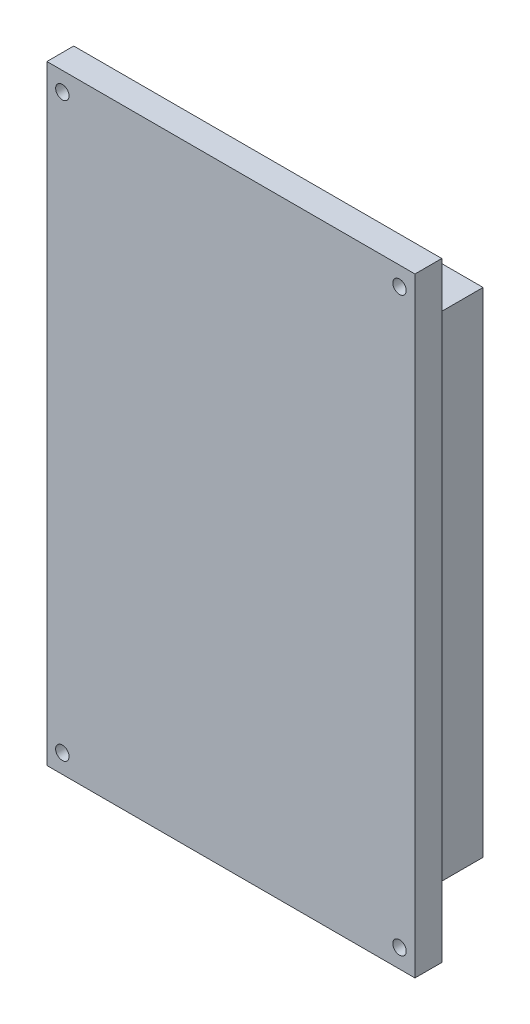
SolidWorks part; units mm, degrees
ref_plane "Front" through (0, 0, 0) normal (0, 0, 1) x (1, 0, 0)
ref_plane "Top" through (0, 0, 0) normal (0, 1, 0) x (1, 0, 0)
ref_plane "Right" through (0, 0, 0) normal (1, 0, 0) x (0, 0, -1)
sketch "arduinoOutline" plane through (0, 0, 0) normal (0, 0, 1) x (1, 0, 0)
  line L0 (0, 32.73) -> (2.54, 35.27) construction
  line L2 (0, 0) -> (0, 32.73) construction
  line L5 (2.54, 35.27) -> (2.54, 36.81) construction
  line L6 (3.54, 37.81) -> (67.6, 37.81) construction
  line L7 (68.6, 36.81) -> (68.6, -14.59) construction
  line L8 (67.6, -15.59) -> (4.06, -15.59) construction
  line L9 (4.06, -15.59) -> (2.54, -14.07) construction
  line L10 (2.54, -14.07) -> (2.54, -2.54) construction
  line L11 (2.54, -2.54) -> (0, 0) construction
  arc A0 (2.54, 36.81) -> (3.54, 37.81) centre (3.54, 36.81) cw construction
  arc A1 (68.6, -14.59) -> (67.6, -15.59) centre (67.6, -14.59) cw construction
  arc A2 (67.6, 37.81) -> (68.6, 36.81) centre (67.6, 36.81) cw construction
  point P8 (2.54, 37.81)
  point P13 (68.6, -15.59)
  point P16 (68.6, 37.81)
  dimension "D6" = 1
  dimension "D9" = 1
  dimension "D10" = 1
  dimension "D1" = 32.73
  dimension "D2" = 135
  dimension "D3" = 3.5921
  dimension "D4" = 2.54
  dimension "D5" = 66.06
  dimension "D7" = 53.4
  dimension "D8" = 64.54
  dimension "D11" = 135
  dimension "D12" = 2.1496
  dimension "D13" = 11.53
  dimension "D14" = 135
  dimension "D15" = 3.5921
sketch "arduinoMountingHolesSketch" plane through (0, 0, 0) normal (0, 0, 1) x (1, 0, 0)
  line L0 (0, 0) -> (0, 32.73) construction
  line L1 (67.6, -15.59) -> (4.06, -15.59) construction
  line L2 (3.54, 37.81) -> (67.6, 37.81) construction
  line L3 (68.6, 36.81) -> (68.6, -14.59) construction
  circle A0 centre (2.54, 2.28) radius 1.25
  circle A1 centre (2.54, 30.45) radius 1.25
  circle A2 centre (54.6, 35.27) radius 1.25
  circle A3 centre (53.35, -13.05) radius 1.25
  dimension "D9" = 2.5
  dimension "D1" = 2.54
  dimension "D2" = 17.87
  dimension "D3" = 2.54
  dimension "D4" = 7.36
  dimension "D5" = 2.54
  dimension "D6" = 14
  dimension "D7" = 2.54
  dimension "D8" = 15.25
sketch "9VbatteryMountingHolesSketch" plane through (0, 0, 0) normal (0, 0, 1) x (1, 0, 0)
  line L0 (0, 16.365) -> (68.6, 16.365) construction
  line L1 (4.875, 40.31) -> (63.725, 40.31) construction
  line L2 (4.875, 40.31) -> (4.875, 88.56) construction
  line L3 (4.875, 88.56) -> (63.725, 88.56) construction
  line L4 (63.725, 40.31) -> (63.725, 88.56) construction
  line L5 (0, 0) -> (0, 32.73) construction
  line L6 (68.6, 36.81) -> (68.6, -14.59) construction
  line L7 (34.3, 40.31) -> (34.3, 88.56) construction
  line L8 (4.875, 64.435) -> (63.725, 64.435) construction
  line L10 (3.54, 37.81) -> (67.6, 37.81) construction
  circle A0 centre (8.625, 86.06) radius 1.25
  circle A1 centre (59.975, 86.06) radius 1.25
  circle A2 centre (8.625, 42.81) radius 1.25
  circle A3 centre (59.975, 42.81) radius 1.25
  point P4 (34.3, 16.365)
  point P5 (34.3, 88.56)
  dimension "D3" = 2.5
  dimension "D1" = 48.25
  dimension "D2" = 58.85
  dimension "D4" = 2.5
  dimension "D5" = 3.75
  dimension "D6" = 2.5
sketch "legBracketMountingHolesSketch" plane through (0, 0, 0) normal (0, 0, 1) x (1, 0, 0)
  line L0 (34.3, 91.06) -> (34.3, 98.06) construction
  line L1 (24.1051, 98.06) -> (44.4949, 98.06) construction
  line L2 (24.1051, 98.06) -> (24.1051, 91.06) construction
  line L3 (24.1051, 91.06) -> (44.4949, 91.06) construction
  line L4 (44.4949, 98.06) -> (44.4949, 91.06) construction
  circle A0 centre (29.2026, 94.56) radius 2
  circle A1 centre (39.3974, 94.56) radius 2
  point P4 (24.1051, 94.56)
  point P5 (34.3, 98.06)
  dimension "D4" = 4
  dimension "D1" = 7
  dimension "D2" = 20.3898
  dimension "D3" = 2.5
  dimension "D5" = 5.0974
sketch "backsideMountingHolesSketch" plane through (0, 0, 0) normal (0, 0, 1) x (1, 0, 0)
  line L0 (0, 41.235) -> (68.6, 41.235) construction
  line L9 (0, 0) -> (0, 32.73) construction
  line L10 (34.3, 40.31) -> (34.3, 88.56) construction
  line L11 (68.6, 36.81) -> (68.6, -14.59) construction
  line L12 (24.1051, 98.06) -> (44.4949, 98.06) construction
  line L13 (4.875, 88.56) -> (63.725, 88.56) construction
  line L14 (4.875, 40.31) -> (4.875, 88.56) construction
  circle A1 centre (2.875, 94.56) radius 1.25
  circle A5 centre (65.725, 94.56) radius 1.25
  circle A6 centre (65.725, -12.09) radius 1.25
  circle A7 centre (2.875, -12.09) radius 1.25
  dimension "D1" = 2.5
  dimension "D2" = 56.825
  dimension "D3" = 6
  dimension "D4" = 2
sketch "Sketch1" plane through (0, 0, 0) normal (0, 0, 1) x (1, 0, 0)
  line L0 (67.6, -15.59) -> (4.06, -15.59) construction
  line L1 (0, 98.06) -> (68.6, 98.06)
  line L2 (0, 98.06) -> (0, -15.59)
  line L3 (0, -15.59) -> (68.6, -15.59)
  line L4 (68.6, 98.06) -> (68.6, -15.59)
  line L5 (0, 0) -> (0, 32.73) construction
  line L6 (68.6, 36.81) -> (68.6, -14.59) construction
  line L9 (24.1051, 98.06) -> (44.4949, 98.06) construction
extrude "bracketBase" add sketch "Sketch1" along normal blind 5
extrude "arduinoMountingHoles" cut sketch "arduinoMountingHolesSketch" against normal through all and the other way blind 22
extrude "9VbatteryMountingHoles" cut sketch "9VbatteryMountingHolesSketch" along normal blind 20
extrude "legBracketMountingHoles" cut sketch "legBracketMountingHolesSketch" along normal blind 13
extrude "backsideMountingHoles" cut sketch "backsideMountingHolesSketch" along normal blind 24
sketch "Sketch2" plane through (0, 0, 5) normal (0, 0, 1) x (1, 0, 0)
  circle A0 centre (53.35, -13.05) radius 1.25 construction
  circle A1 centre (2.54, 2.28) radius 1.25 construction
  circle A2 centre (2.54, 30.45) radius 1.25 construction
  circle A3 centre (54.6, 35.27) radius 1.25 construction
  circle A4 centre (59.975, 42.81) radius 1.25 construction
  circle A5 centre (8.625, 42.81) radius 1.25 construction
  circle A6 centre (59.975, 86.06) radius 1.25 construction
  circle A7 centre (39.3974, 94.56) radius 2 construction
  circle A8 centre (29.2026, 94.56) radius 2 construction
  circle A9 centre (8.625, 86.06) radius 1.25 construction
  circle A10 centre (53.35, -13.05) radius 1.25
  circle A11 centre (2.54, 2.28) radius 1.25
  circle A12 centre (2.54, 30.45) radius 1.25
  circle A13 centre (54.6, 35.27) radius 1.25
  circle A14 centre (59.975, 42.81) radius 1.25
  circle A15 centre (8.625, 42.81) radius 1.25
  circle A16 centre (59.975, 86.06) radius 1.25
  circle A17 centre (39.3974, 94.56) radius 2
  circle A18 centre (29.2026, 94.56) radius 2
  circle A19 centre (8.625, 86.06) radius 1.25
extrude "cover" add sketch "Sketch2" against normal up to surface (5 mm away) up to face at (1.625, -12.09, 0)
sketch "Sketch3" plane through (0, 0, 5) normal (0, 0, 1) x (1, 0, 0)
  line L0 (34.3, -15.59) -> (34.3, 98.06) construction
  line L1 (0, -15.59) -> (68.6, -15.59) construction
  line L2 (68.6, 98.06) -> (0, 98.06) construction
  line L3 (2.3, -4.765) -> (2.3, 87.235)
  line L4 (5.3, -1.765) -> (63.3, -1.765)
  line L5 (5.3, -1.765) -> (5.3, 84.235)
  line L6 (5.3, 84.235) -> (63.3, 84.235)
  line L7 (63.3, -1.765) -> (63.3, 84.235)
  line L8 (5.3, -1.765) -> (63.3, 84.235) construction
  line L9 (5.3, 84.235) -> (63.3, -1.765) construction
  line L10 (2.3, 87.235) -> (66.3, 87.235)
  line L11 (66.3, -4.765) -> (66.3, 87.235)
  line L12 (2.3, -4.765) -> (66.3, -4.765)
  point P6 (34.3, 41.235)
  dimension "D1" = 86
  dimension "D2" = 58
  dimension "D3" = 3
extrude "breadBoardCavity" add sketch "Sketch3" along normal blind 10
ref_plane "Plane1" through (0, 0, 2.5) normal (0, 0, 1) x (1, 0, 0)
mirror "Mirror1" about plane through (0, 0, 2.5) normal (0, 0, 1) of "breadBoardCavity"
sketch "Sketch4" plane through (0, 87.235, 0) normal (0, 1, 0) x (1, 0, 0)
  line L4 (66.3, -5) -> (2.3, -5)
  line L5 (2.3, -5) -> (2.3, -15)
  line L6 (2.3, -15) -> (66.3, -15)
  line L7 (66.3, -15) -> (66.3, -5)
  line L8 (66.3, -5) -> (2.3, -5)
  line L9 (2.3, -5) -> (2.3, -15)
  line L10 (2.3, -15) -> (66.3, -15)
  line L11 (66.3, -15) -> (66.3, -5)
  dimension "D1" = 0
extrude "Cut-Extrude1" cut sketch "Sketch4" against normal through all
equation "\"D2@backsideMountingHolesSketch\"=113.65mm/2"
